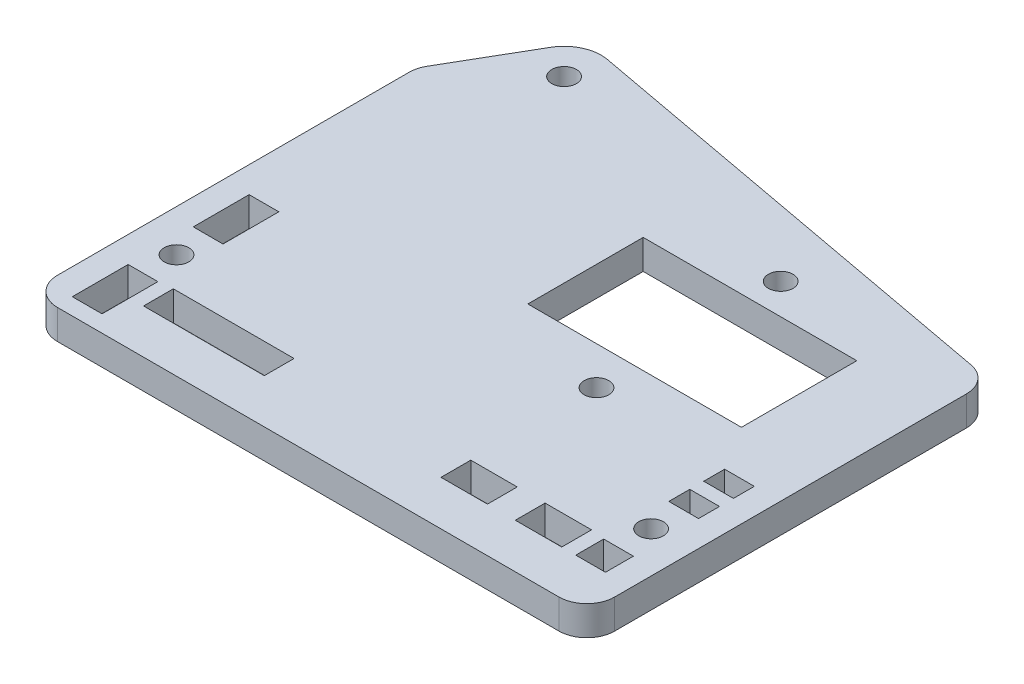
SolidWorks part; units mm, degrees
ref_plane "Front Plane" through (0, 0, 0) normal (0, 0, 1) x (1, 0, 0)
ref_plane "Top Plane" through (0, 0, 0) normal (0, 1, 0) x (1, 0, 0)
ref_plane "Right Plane" through (0, 0, 0) normal (1, 0, 0) x (0, 0, -1)
sketch "Sketch1" plane through (0, 0, 0) normal (0, 1, 0) x (1, 0, 0)
  line L0 (22.4482, -10.4787) -> (22.4482, -10.4849)
  line L1 (22.4482, -10.4849) -> (22.4482, -12.7319)
  line L2 (22.4482, -12.7319) -> (25.6427, -12.7319)
  line L3 (25.6427, -12.7319) -> (25.6427, -10.4787)
  line L4 (25.6427, -10.4787) -> (22.4482, -10.4787)
  line L5 (22.4482, -22.7324) -> (25.6427, -22.7324)
  line L6 (25.6427, -22.7324) -> (25.6427, -19.7322)
  line L7 (25.6427, -19.7322) -> (22.4482, -19.7322)
  line L8 (22.4482, -19.7322) -> (22.4482, -22.7324)
  line L9 (-25.4666, -12.7319) -> (-25.4666, -6.7316)
  line L10 (-25.4666, -6.7316) -> (-28.661, -6.7316)
  line L11 (-28.661, -6.7316) -> (-28.661, -12.7319)
  line L12 (-28.661, -12.7319) -> (-25.4666, -12.7319)
  line L13 (-25.4666, -25.7324) -> (-25.4666, -19.7322)
  line L14 (-25.4666, -19.7322) -> (-28.661, -19.7322)
  line L15 (-28.661, -19.7322) -> (-28.661, -25.7324)
  line L16 (-28.661, -25.7324) -> (-25.4666, -25.7324)
  line L17 (15.951, -22.7324) -> (15.951, -19.5323)
  line L18 (15.951, -19.5323) -> (20.942, -19.5323)
  line L19 (20.942, -19.5323) -> (20.942, -22.7324)
  line L20 (20.942, -22.7324) -> (15.951, -22.7324)
  line L21 (12.9563, -22.7324) -> (7.9651, -22.7324)
  line L22 (7.9651, -22.7324) -> (7.9651, -19.5323)
  line L23 (7.9651, -19.5323) -> (12.9563, -19.5323)
  line L24 (12.9563, -19.5323) -> (12.9563, -22.7324)
  line L25 (25.4429, -27.5324) -> (-28.4561, -27.5324)
  line L26 (-31.456, -24.5325) -> (-31.456, 13.2693)
  line L27 (-31.0509, 14.776) -> (-26.1748, 23.1862)
  line L28 (-21.9978, 25.1075) -> (25.9832, 16.22)
  line L29 (28.4378, 13.269) -> (28.4376, -24.5377)
  line L30 (-10.9933, -19.5326) -> (-10.9933, -19.5668)
  line L31 (-10.9933, -19.5668) -> (-23.9701, -19.5668)
  line L32 (-23.9701, -19.5668) -> (-23.9701, -22.767)
  line L33 (-23.9701, -22.767) -> (-10.9933, -22.767)
  line L34 (-10.9933, -22.767) -> (-10.9933, -19.5326)
  line L35 (19.4537, -1.9316) -> (-3.5057, -1.9316)
  line L36 (-3.5057, -1.9316) -> (-3.5057, 10.469)
  line L37 (-3.5057, 10.469) -> (19.4537, 10.469)
  line L38 (19.4537, 10.469) -> (19.4537, -1.9316)
  line L39 (25.6427, -6.7255) -> (25.6427, -6.7316)
  line L40 (25.6427, -6.7316) -> (22.4482, -6.7316)
  line L41 (22.4482, -6.7316) -> (22.4482, -8.9787)
  line L42 (22.4482, -8.9787) -> (25.6427, -8.9787)
  line L43 (25.6427, -8.9787) -> (25.6427, -6.7255)
  arc A0 (-31.456, -24.5325) -> (-28.4561, -27.5324) centre (-28.4561, -24.5325) ccw
  arc A1 (25.4429, -27.5324) -> (28.4376, -24.5377) centre (25.4429, -24.5377) ccw
  arc A2 (28.4378, 13.269) -> (25.9832, 16.22) centre (25.4366, 13.269) ccw
  arc A3 (-21.9978, 25.1075) -> (-26.1748, 23.1862) centre (-22.7242, 21.1856) ccw
  arc A4 (-31.0509, 14.776) -> (-31.456, 13.2693) centre (-28.4522, 13.2693) ccw
  circle A5 centre (-22.7242, 21.1856) radius 1.323
  circle A6 centre (-26.964, -16.2321) radius 1.323
  circle A7 centre (7.974, 13.769) radius 1.323
  circle A8 centre (7.974, -6.0315) radius 1.323
  circle A9 centre (24.0455, -16.2321) radius 1.323
  point P5 (-26.964, -16.2321)
  point P7 (7.974, -6.0315)
  point P8 (24.0455, -16.2321)
  point P9 (7.974, 13.769)
  dimension "D1" = 2.6461
extrude "Boss-Extrude1" add sketch "Sketch1" along normal blind 3.175 contours L27 A4 L26 A0 L25 A1 L29 A2 L28 A3 A9 A8 A7 A6 A5 L37 L38 L35 L36 L23 L24 L21 L22 L19 L20 L17 L18 L4 L3 L2 L1 L0 L8 L7 L6 L5 L12 L11 L10 L9 region at (-3.28, 0, 3.4465)
